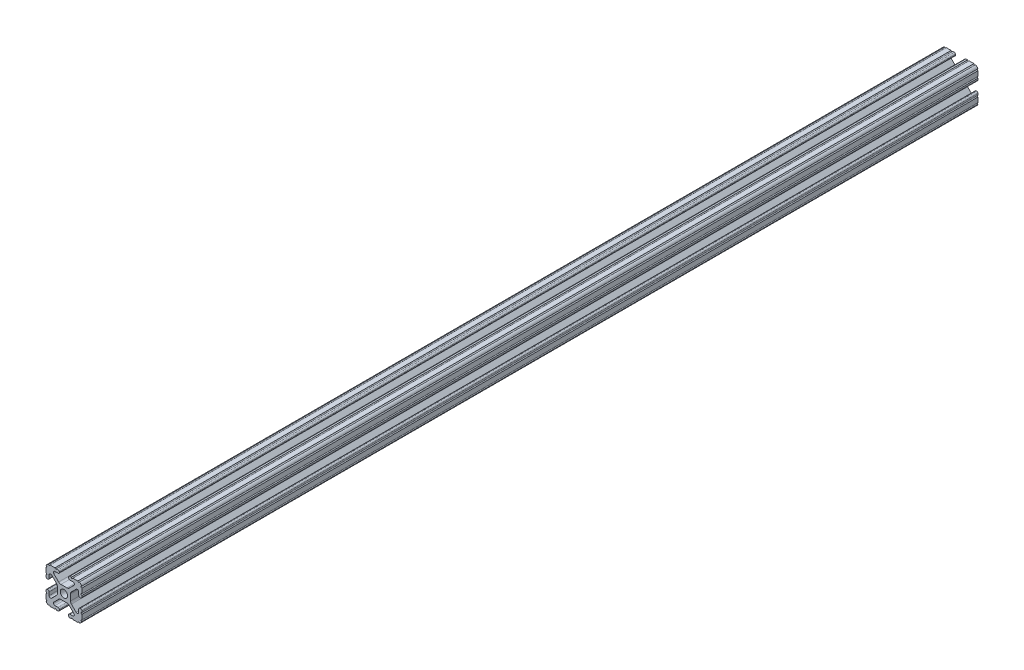
SolidWorks part; units mm, degrees
ref_plane "Front Plane" through (0, 0, 0) normal (0, 0, 1) x (1, 0, 0)
ref_plane "Top Plane" through (0, 0, 0) normal (0, 1, 0) x (1, 0, 0)
ref_plane "Right Plane" through (0, 0, 0) normal (1, 0, 0) x (0, 0, -1)
sketch "Sketch2" plane through (0, 0, 0) normal (0, 0, 1) x (1, 0, 0)
  line L0 (0, 12.7) -> (0, -12.7) construction
  line L1 (-12.7, 0) -> (12.7, 0) construction
  line L2 (3.2512, -12.7) -> (12.7, -12.7)
  line L3 (12.7, -12.7) -> (12.7, -3.2512)
  line L4 (3.2512, -12.7) -> (3.2512, -10.4902)
  line L5 (3.2512, -10.4902) -> (8.9276, -10.4902)
  line L6 (8.9276, -10.4902) -> (3.0856, -4.6482)
  line L7 (0, 0) -> (12.7, -12.7) construction
  line L8 (12.7, -3.2512) -> (10.4902, -3.2512)
  line L9 (10.4902, -3.2512) -> (10.4902, -8.9276)
  line L10 (10.4902, -8.9276) -> (4.6482, -3.0856)
  circle A0 centre (0, 0) radius 2.6035
  arc A1 (6.3485, -10.4902) -> (7.1039, -8.6665) centre (6.3485, -9.4219) ccw construction
  point P8 (0, -4.6482)
  dimension "Center Hole Diameter" = 5.207
  dimension "Rail Height" = 25.4
  dimension "Rail Width" = 25.4
  dimension "T-Slot Width" = 6.5024
  dimension "Slot Inner Width" = 14.8336
  dimension "Thickness" = 2.2098
  dimension "Slot Depth" = 5.842
  dimension "D1" = 2.2098
sketch "Sketch3" plane through (0, 0, 0) normal (1, 0, 0) x (0, 0, -1)
  line L0 (-1524, -12.7) -> (1524, -12.7) construction
  line L1 (-1498.6, 0) -> (1498.6, 0) construction
  dimension "Length" = 3048
  dimension "D1" = 25.4
sketch "Sketch4" plane through (0, 0, 0) normal (0, 0, 1) x (1, 0, 0)
  line L0 (4.1904, -12.7) -> (10.1173, -12.7)
  line L1 (3.2512, -12.7) -> (12.7, -12.7) construction
  line L2 (3.2512, -12.7) -> (3.2512, -10.4902) construction
  line L3 (3.2512, -10.4902) -> (8.9276, -10.4902) construction
  line L4 (3.2512, -11.4294) -> (3.2512, -11.7608)
  line L5 (4.1904, -10.4902) -> (6.3485, -10.4902)
  line L6 (0, -4.6482) -> (2.164, -4.6482)
  line L7 (8.9276, -10.4902) -> (3.0856, -4.6482) construction
  line L8 (3.7373, -5.2999) -> (7.1039, -8.6665)
  line L9 (12.7, -12.7) -> (12.7, -3.2512) construction
  line L10 (10.4902, -8.9276) -> (4.6482, -3.0856) construction
  line L11 (10.4902, -3.2512) -> (10.4902, -8.9276) construction
  line L12 (10.4902, -6.3485) -> (10.4902, -4.1904)
  line L13 (12.7, -3.2512) -> (10.4902, -3.2512) construction
  line L14 (11.4294, -3.2512) -> (11.7608, -3.2512)
  line L15 (12.7, -4.1904) -> (12.7, -10.1173)
  line L16 (8.6665, -7.1039) -> (5.2999, -3.7373)
  line L17 (4.6482, 0) -> (4.6482, -2.164)
  line L18 (-12.7, 0) -> (12.7, 0) construction
  line L19 (0, -4.6482) -> (0, -2.6035)
  line L20 (0, 12.7) -> (0, -12.7) construction
  line L21 (4.6482, 0) -> (2.6035, 0)
  arc A0 (3.2512, -11.7608) -> (4.1904, -12.7) centre (4.1904, -11.7608) ccw
  arc A2 (3.2512, -11.4294) -> (4.1904, -10.4902) centre (4.1904, -11.4294) cw
  arc A3 (6.3485, -10.4902) -> (7.1039, -8.6665) centre (6.3485, -9.4219) ccw
  arc A4 (2.164, -4.6482) -> (3.7373, -5.2999) centre (2.164, -6.8732) cw
  arc A5 (10.1173, -12.7) -> (12.7, -10.1173) centre (10.1173, -10.1173) ccw
  arc A6 (8.6665, -7.1039) -> (10.4902, -6.3485) centre (9.4219, -6.3485) ccw
  arc A7 (10.4902, -4.1904) -> (11.4294, -3.2512) centre (11.4294, -4.1904) cw
  arc A8 (11.7608, -3.2512) -> (12.7, -4.1904) centre (11.7608, -4.1904) cw
  arc A9 (5.2999, -3.7373) -> (4.6482, -2.164) centre (6.8732, -2.164) cw
  circle A10 centre (0, 0) radius 2.6035 construction
  arc A11 (0, -2.6035) -> (2.6035, 0) centre (0, 0) ccw
  dimension "D1" = 2.5827
  dimension "D2" = 2.225
  dimension "D3" = 0.9392
extrude "Boss-Extrude1" add sketch "Sketch4" along normal mid plane 3048
sketch "Sketch5" plane through (0, 0, 0) normal (0, 0, 1) x (1, 0, 0)
  line L0 (3.2512, -12.7) -> (12.7, -12.7) construction
  line L1 (4.1904, -10.4902) -> (6.3485, -10.4902) construction
  line L3 (0, 0) -> (12.7, -12.7) construction
  line L4 (6.3485, -10.4902) -> (6.3485, -12.7) construction
  line L5 (8.9276, -10.4902) -> (3.0856, -4.6482) construction
  circle A0 centre (10.3562, -12.7) radius 0.5524
  circle A1 centre (5.796, -12.7) radius 0.5524
  circle A2 centre (12.7, -10.3562) radius 0.5524
  circle A3 centre (12.7, -5.796) radius 0.5524
  point P10 (5.2694, -10.4902)
  point P12 (9.4219, -6.3485)
  dimension "D1" = 1.1049
extrude "Cut-Extrude1" cut sketch "Sketch5" against normal through all both and the other way through all
mirror "Mirror1" about plane through (0, 0, 0) normal (1, 0, 0) of bodies 137 134
mirror "Mirror2" about plane through (0, 0, 0) normal (0, 1, 0) of bodies 135
sketch "Sketch8" plane through (0, 0, 0) normal (0, 1, 0) x (1, 0, 0)
  line L0 (-12.58, 1524) -> (-12.58, -1524) construction
  line L1 (-25.28, 1536.7) -> (25.28, 1536.7)
  line L2 (-25.28, 1536.7) -> (-25.28, 304.8)
  line L3 (-25.28, 304.8) -> (25.28, 304.8)
  line L4 (25.28, 1536.7) -> (25.28, 304.8)
  line L5 (12.58, 1524) -> (12.58, -1524) construction
  line L6 (-6.3485, 1524) -> (-9.8037, 1524) construction
  dimension "D1" = 12.7
  dimension "D2" = 12.7
  dimension "D3" = 12.7
  dimension "D4" = 1219.2
extrude "Cut-Extrude2" cut sketch "Sketch8" against normal through all both and the other way through all
sketch "Sketch9" plane through (0, 0, 0) normal (0, 1, 0) x (1, 0, 0)
  line L0 (6.3485, -1524) -> (9.8037, -1524) construction
  line L1 (-25.4, 317.5) -> (25.28, 317.5)
  line L2 (-25.4, 317.5) -> (-25.4, -889)
  line L3 (-25.4, -889) -> (25.28, -889)
  line L4 (25.28, 317.5) -> (25.28, -889)
  line L5 (-9.8037, 304.8) -> (-6.3485, 304.8) construction
  line L7 (-12.7, 304.8) -> (-12.7, -1524) construction
  line L8 (12.58, 304.8) -> (12.58, -1524) construction
  dimension "D1" = 635
  dimension "D2" = 12.7
  dimension "D3" = 12.7
  dimension "D4" = 12.7
extrude "Cut-Extrude3" cut sketch "Sketch9" against normal through all both and the other way through all
equation "\"D1@Boss-Extrude1\"=\"Length@Sketch3\""
equation "\"D1@Sketch2\"=\"Thickness@Sketch2\""
equation "\"D2@Sketch4\"=\"Slot Inner Width@Sketch2\"*0.15"
equation "\"D1@Sketch4\"=\"D3@Sketch4\"*2.75"
equation "\"D3@Sketch4\"=\"Thickness@Sketch2\"*0.425"
equation "\"D1@Sketch5\"=\"Thickness@Sketch2\"*0.5"
